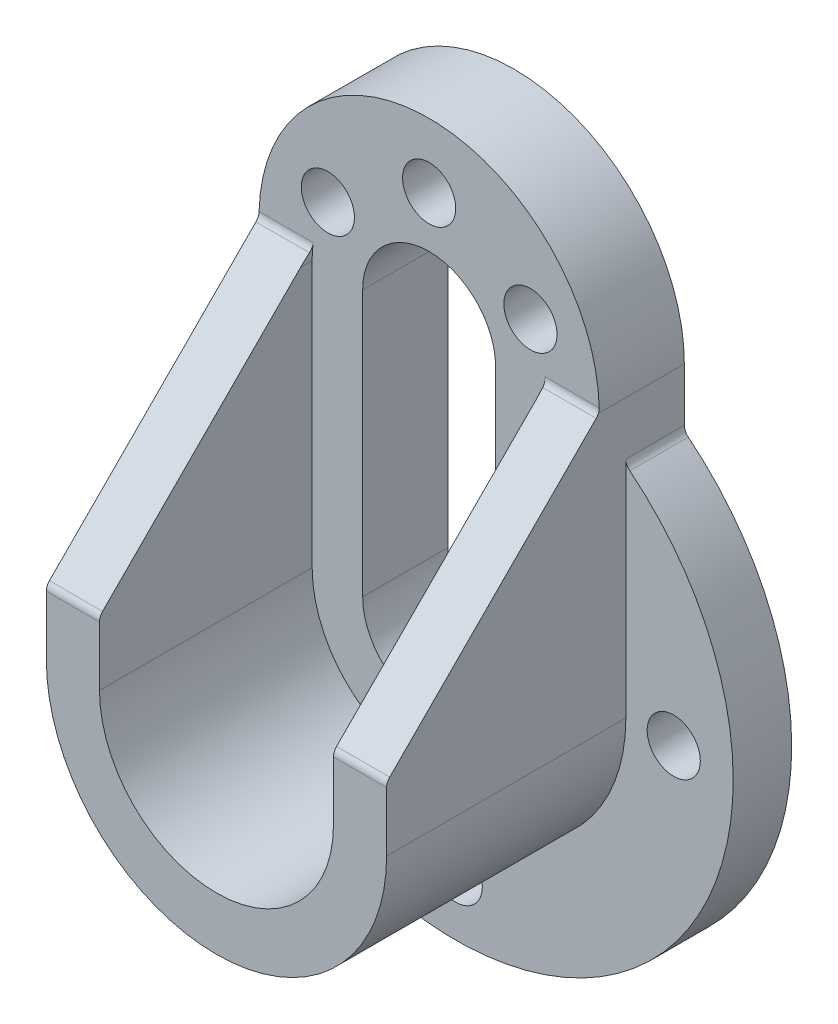
SolidWorks part; units mm, degrees
ref_plane "Front Plane" through (0, 0, 0) normal (0, 0, 1) x (1, 0, 0)
ref_plane "Top Plane" through (0, 0, 0) normal (0, 1, 0) x (1, 0, 0)
ref_plane "Right Plane" through (0, 0, 0) normal (1, 0, 0) x (0, 0, -1)
sketch "Sketch1" plane through (0, 0, 0) normal (0, 0, 1) x (1, 0, 0)
  line L0 (0, 0) -> (0, 52.1878) construction
  line L1 (-32, 0) -> (-32, 52.1878)
  line L2 (32, 0) -> (32, 52.1878)
  arc A0 (-32, 0) -> (32, 0) centre (0, 0) ccw
  arc A1 (32, 52.1878) -> (-32, 52.1878) centre (0, 52.1878) ccw
  circle A2 centre (0, 0) radius 52.1878
  point P3 (0, 26.0939)
  dimension "D1" = 32
  dimension "D2" = 104.3757
extrude "Boss-Extrude1" add sketch "Sketch1" against normal blind 16 and the other way blind 40 contours L2 A2 L1 A0 | A2 L2 A1 L1 region at (0, 11.5092, 0) region at (0, 63.723, 0)
extrude "Boss-Extrude2" add sketch "Sketch1<3>" against normal blind 11 from offset 5 contours A2 offset against normal yes
sketch "Sketch1<3>" plane through (0, 0, 0) normal (0, 0, 1) x (1, 0, 0) same geometry as "Sketch1"
sketch "Sketch2" plane through (0, 0, 40) normal (0, 0, 1) x (1, 0, 0)
  line L0 (0, 0) -> (0, 50) construction
  line L1 (-12.5, 0) -> (-12.5, 50)
  line L2 (12.5, 0) -> (12.5, 50)
  arc A0 (-12.5, 0) -> (12.5, 0) centre (0, 0) ccw
  arc A1 (12.5, 50) -> (-12.5, 50) centre (0, 50) ccw
  point P3 (0, 25)
  dimension "D1" = 12.5
  dimension "D2" = 25
extrude "Cut-Extrude1" cut sketch "Sketch2" against normal through all
sketch "Sketch6" plane through (0, 0, 40) normal (0, 0, 1) x (1, 0, 0)
  line L0 (0, 0) -> (0, 50) construction
  line L1 (-22, 0) -> (-22, 50)
  line L2 (22, 0) -> (22, 50)
  arc A0 (-22, 0) -> (22, 0) centre (0, 0) ccw
  arc A1 (22, 50) -> (-22, 50) centre (0, 50) ccw
  point P3 (0, 25)
  dimension "D1" = 22
  dimension "D2" = 25
extrude "Cut-Extrude3" cut sketch "Sketch6" against normal blind 40
sketch "Sketch7" plane through (32, 0, 0) normal (1, 0, 0) x (0, 0, -1)
  line L1 (-40, 0) -> (-40, 52.1878) construction
  line L2 (0, 52.1878) -> (0, 84.1878)
  line L3 (-40, 52.1878) -> (16, 52.1878) construction
  line L4 (0, 52.1878) -> (-40, 12)
  line L5 (16, 84.1878) -> (-40, 84.1878) construction
  line L6 (0, 84.1878) -> (-40, 84.1878)
  line L7 (-40, 84.1878) -> (-40, 52.1878) construction
  line L8 (-40, 84.1878) -> (-40, 12)
  line L9 (5, 41.2258) -> (16, 41.2258) construction
  dimension "D1" = 29.2258
extrude "Cut-Extrude4" cut sketch "Sketch7" against normal through all
fillet "Fillet1" radius 2 2 edges at (27, 12, 40) (-27, 12, 40)
sketch "Sketch12" plane through (0, 0, 0) normal (0, 0, 1) x (1, 0, 0)
  line L0 (0, 72) -> (0, 50) construction
  line L1 (0, 50) -> (19.0526, 61) construction
  line L2 (0, 50) -> (-19.0526, 61) construction
  line L4 (-32, 52.1878) -> (-21.8909, 52.1878) construction
  circle A0 centre (0, 50) radius 22
  circle A1 centre (0, 72) radius 4.9149
  dimension "D1" = 9.8298
  dimension "D2" = 44
  dimension "D3" = 8.8122
hole_wizard "Ø10.0mm Dowel Hole1" positions "Sketch22" profile "Sketch23" hole size "Ø10.0" standard "ANSI Metric" end condition through all
sketch "Sketch22" plane through (0, 0, 0) normal (0, 0, 1) x (1, 0, 0)
  point P0 (-19.0526, 61)
  point P3 (19.0526, 61)
  point P7 (0, 72)
sketch "Sketch23" plane through (-19.0526, 61, 0) normal (1, 0, 0) x (0, -1, 0)
  line L0 (0, 0) -> (0, 16)
  line L1 (0, 16) -> (5, 16)
  line L2 (5, 16) -> (5, 0)
  line L5 (5, 0) -> (0, 0)
  line L11 (0, -6.35) -> (0, 107.95) construction
  dimension "Thru Hole Dia." = 10
  dimension "Thru Hole Depth" = 16
sketch "Sketch28" plane through (0, 0, -16) normal (0, 0, -1) x (-1, 0, 0)
  circle A0 centre (0, 0) radius 41
  dimension "D1" = 82
hole_wizard "Ø10.0mm Dowel Hole2" positions "Sketch29" profile "Sketch30" hole size "Ø10.0" standard "ANSI Metric" end condition through all
sketch "Sketch29" plane through (0, 0, -16) normal (0, 0, -1) x (-1, 0, 0)
  line L0 (-12.5, 0) -> (-12.5, 50) construction
  circle A0 centre (0, 0) radius 41 construction
  point P0 (0, -41)
  point P4 (41, 0)
  point P6 (-41, 0)
  dimension "D1" = 12.5
sketch "Sketch30" plane through (0, -41, -16) normal (1, 0, 0) x (0, 1, 0)
  line L0 (0, 0) -> (0, 56)
  line L1 (0, 56) -> (5, 56)
  line L2 (5, 56) -> (5, 0)
  line L5 (5, 0) -> (0, 0)
  line L11 (0, -6.35) -> (0, 107.95) construction
  dimension "Thru Hole Dia." = 10
  dimension "Thru Hole Depth" = 56
fillet "Fillet2" radius 2 2 edges at (26.9455, 52.1878, 0) (-26.9455, 52.1878, 0)
fillet "Fillet3" radius 2 2 edges at (-32, 41.2258, -10.5) (32, 41.2258, -10.5)
